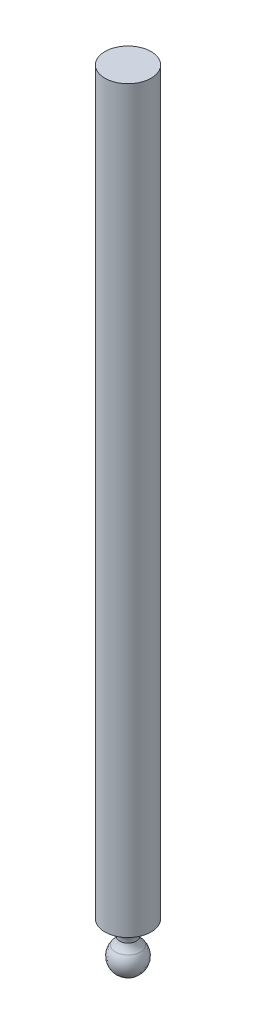
SolidWorks part; units mm, degrees
ref_plane "Спереди" through (0, 0, 0) normal (0, 0, 1) x (1, 0, 0)
ref_plane "Сверху" through (0, 0, 0) normal (0, 1, 0) x (1, 0, 0)
ref_plane "Справа" through (0, 0, 0) normal (1, 0, 0) x (0, 0, -1)
sketch "Эскиз3" plane through (0, 0, 0) normal (1, 0, 0) x (0, 0, -1)
  line L0 (0, 11.108) -> (0, -11.8568) construction
  line L1 (-7.5, 0) -> (0, 0)
  line L2 (0, 0) -> (0, -15.4469)
  arc A0 (0, -15.4469) -> (-4.061, -7.3279) centre (-0.155, -10.4493) cw
  arc A1 (-2.6894, -4.9864) -> (-4.061, -7.3279) centre (-7.5844, -3.6914) cw
  arc A2 (-2.6894, -4.9864) -> (-7.5, 0) centre (-7.7337, -5.0392) ccw
  point P8 (0, 0)
  point P9 (0, 0)
revolve "Повернуть1" add sketch "Эскиз3" angle 360 about L0
sketch "Эскиз4" plane through (0, 0, 0) normal (0, 1, 0) x (1, 0, 0)
  circle A0 centre (0, 0) radius 7.5
extrude "Бобышка-Вытянуть1" add sketch "Эскиз4" along normal blind 240
